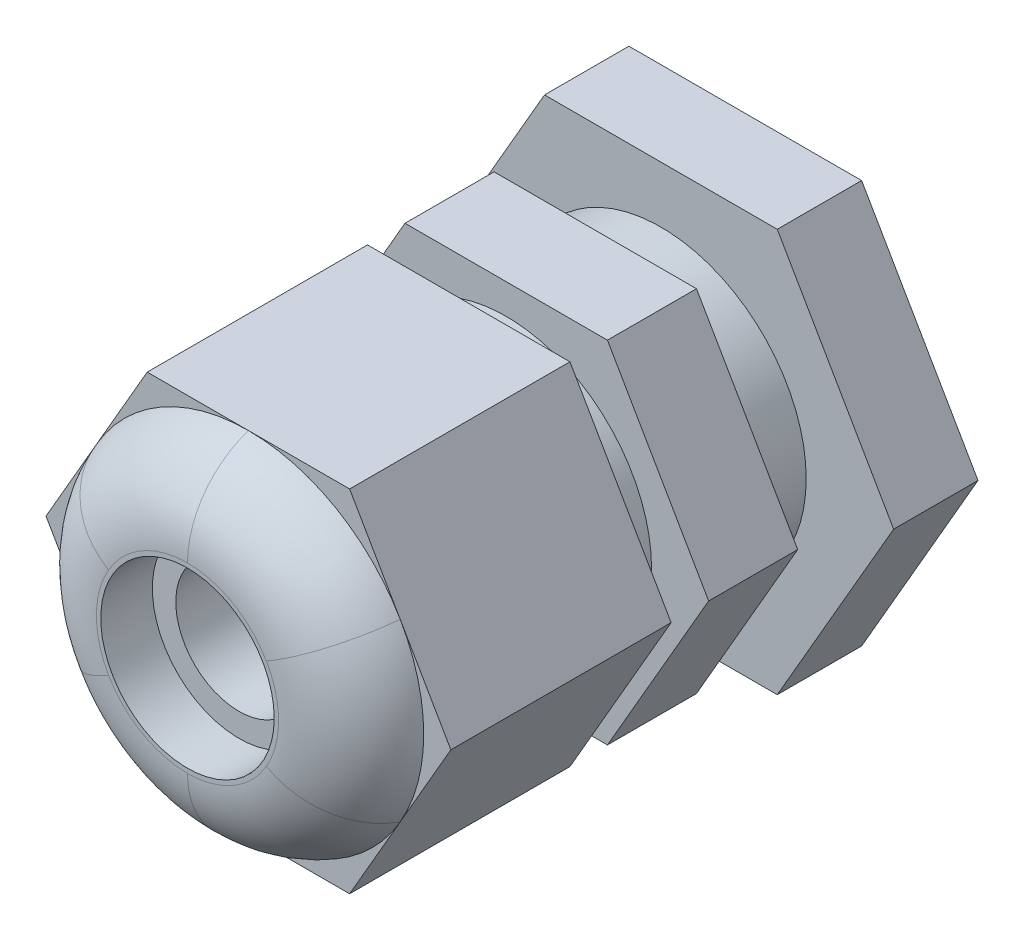
SolidWorks part; units mm, degrees
ref_plane "Front Plane" through (0, 0, 0) normal (0, 0, 1) x (1, 0, 0)
ref_plane "Top Plane" through (0, 0, 0) normal (0, 1, 0) x (1, 0, 0)
ref_plane "Right Plane" through (0, 0, 0) normal (1, 0, 0) x (0, 0, -1)
sketch "Sketch1" plane through (0, 0, 0) normal (0, 0, 1) x (1, 0, 0)
  line L1 (10.7965, 0) -> (5.3982, 9.35)
  line L2 (5.3982, 9.35) -> (-5.3982, 9.35)
  line L3 (-5.3982, 9.35) -> (-10.7965, 0)
  line L4 (-10.7965, 0) -> (-5.3982, -9.35)
  line L5 (-5.3982, -9.35) -> (5.3982, -9.35)
  line L6 (5.3982, -9.35) -> (10.7965, 0)
  circle A0 centre (0, 0) radius 9.35 construction
  point P1 (10.7537, 0.9601)
  dimension "D1" = 18.7
extrude "Boss-Extrude1" add sketch "Sketch1" along normal blind 11.75
sketch "Sketch2" plane through (0, 0, 0) normal (0, 0, -1) x (-1, 0, 0)
  circle A0 centre (0, 0) radius 7.75
  dimension "D1" = 15.5
extrude "Boss-Extrude2" add sketch "Sketch2" along normal blind 2
sketch "Sketch3" plane through (0, 0, -2) normal (0, 0, -1) x (-1, 0, 0)
  line L1 (10.7965, 0) -> (5.3982, 9.35)
  line L2 (5.3982, 9.35) -> (-5.3982, 9.35)
  line L3 (-5.3982, 9.35) -> (-10.7965, 0)
  line L4 (-10.7965, 0) -> (-5.3982, -9.35)
  line L5 (-5.3982, -9.35) -> (5.3982, -9.35)
  line L6 (5.3982, -9.35) -> (10.7965, 0)
  circle A0 centre (0, 0) radius 9.35 construction
  point P1 (11.6664, 0)
extrude "Boss-Extrude3" add sketch "Sketch3" along normal blind 4.75
sketch "Sketch4" plane through (0, 0, -6.75) normal (0, 0, -1) x (-1, 0, 0)
  circle A0 centre (0, 0) radius 7.75
  dimension "D1" = 15.5
extrude "Boss-Extrude4" add sketch "Sketch4" along normal blind 3.5
sketch "Sketch5" plane through (0, 0, -10.25) normal (0, 0, -1) x (-1, 0, 0)
  line L1 (12.413, 0) -> (6.2065, 10.75)
  line L2 (6.2065, 10.75) -> (-6.2065, 10.75)
  line L3 (-6.2065, 10.75) -> (-12.413, 0)
  line L4 (-12.413, 0) -> (-6.2065, -10.75)
  line L5 (-6.2065, -10.75) -> (6.2065, -10.75)
  line L6 (6.2065, -10.75) -> (12.413, 0)
  circle A0 centre (0, 0) radius 10.75 construction
  point P1 (0, 0)
  dimension "D1" = 21.5
extrude "Boss-Extrude5" add sketch "Sketch5" along normal blind 4.5
sketch "Sketch6" plane through (0, 0, -14.75) normal (0, 0, -1) x (-1, 0, 0)
  circle A0 centre (0, 0) radius 7.75
  dimension "D1" = 15.5
extrude "Boss-Extrude6" add sketch "Sketch6" along normal blind 1.25
sketch "Sketch7" plane through (0, 0, -16) normal (0, 0, -1) x (-1, 0, 0)
  circle A0 centre (0, 0) radius 5.75
  dimension "D1" = 11.5
extrude "Cut-Extrude1" cut sketch "Sketch7" against normal blind 20
sketch "Sketch8" plane through (0, 0, 11.75) normal (0, 0, 1) x (1, 0, 0)
  line L0 (5.3982, 9.35) -> (-5.3982, 9.35) construction
  circle A0 centre (0, 0) radius 9.35
extrude "Boss-Extrude7" add sketch "Sketch8" along normal blind 3.25
sketch "Sketch9" plane through (0, 0, 15) normal (0, 0, 1) x (1, 0, 0)
  circle A0 centre (0, 0) radius 4.625
  dimension "D1" = 9.25
extrude "Cut-Extrude2" cut sketch "Sketch9" against normal blind 2.75
fillet "Fillet2" radius 4.725 1 edges at (9.35, 0, 15)
sketch "Sketch10" plane through (0, 0, 12.25) normal (0, 0, 1) x (1, 0, 0)
  circle A0 centre (0, 0) radius 3.375
  dimension "D1" = 6.75
extrude "Cut-Extrude3" cut sketch "Sketch10" against normal through all
